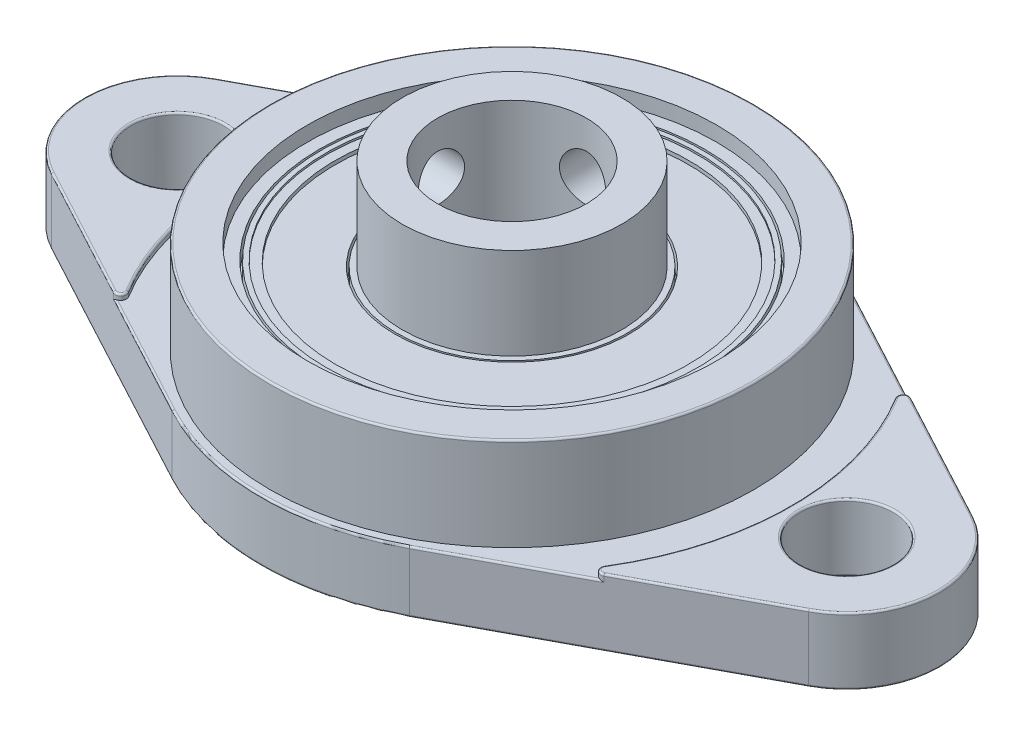
SolidWorks part; units mm, degrees
material "Q235"
ref_plane "前视" through (0, 0, 0) normal (0, 0, 1) x (1, 0, 0)
ref_plane "上视" through (0, 0, 0) normal (0, 1, 0) x (1, 0, 0)
ref_plane "右视" through (0, 0, 0) normal (1, 0, 0) x (0, 0, -1)
sketch "草图1" plane through (0, 0, 0) normal (0, 1, 0) x (1, 0, 0)
  line L0 (0, 0) -> (0, 23.9967) construction
  line L1 (-6.375, 11.9) -> (-20.3611, 4.4074)
  line L2 (0, 0) -> (-38.6632, 0) construction
  line L3 (-6.375, -11.9) -> (-20.3611, -4.4074)
  line L4 (6.375, -11.9) -> (20.3611, -4.4074)
  line L5 (6.375, 11.9) -> (20.3611, 4.4074)
  arc A0 (6.375, 11.9) -> (-6.375, 11.9) centre (0, 0) ccw
  arc A1 (20.3611, -4.4074) -> (20.3611, 4.4074) centre (18, 0) ccw
  circle A2 centre (18, 0) radius 2.5
  circle A3 centre (-18, 0) radius 2.5
  arc A4 (-20.3611, -4.4074) -> (-20.3611, 4.4074) centre (-18, 0) cw
  arc A5 (-6.375, -11.9) -> (6.375, -11.9) centre (0, 0) ccw
  circle A6 centre (0, 0) radius 4
  circle A7 centre (0, 0) radius 13.5 construction
  dimension "D1" = 27
  dimension "D2" = 10
  dimension "D4" = 5
  dimension "D5" = 8
  dimension "D6" = 27
  dimension "D3" = 36
extrude "凸台-拉伸1" add sketch "草图1" along normal blind 3.3
sketch "草图2" plane through (0, 3.3, 0) normal (0, 1, 0) x (1, 0, 0)
  line L0 (-6.375, 11.9) -> (-20.3611, 4.4074) construction
  line L1 (-13.1944, 8.2467) -> (-20.3611, 4.4074)
  line L2 (-20.3611, -4.4074) -> (-6.375, -11.9) construction
  line L3 (-20.3611, -4.4074) -> (-13.1944, -8.2467)
  line L4 (6.375, -11.9) -> (20.3611, -4.4074) construction
  line L5 (13.1944, -8.2467) -> (20.3611, -4.4074)
  line L6 (20.3611, 4.4074) -> (6.375, 11.9) construction
  line L7 (20.3611, 4.4074) -> (13.1944, 8.2467)
  circle A0 centre (0, 0) radius 13.5 construction
  arc A1 (-12.7968, 7.8258) -> (-12.7968, -7.8258) centre (0, 0) ccw
  arc A2 (-20.3611, 4.4074) -> (-20.3611, -4.4074) centre (-18, 0) ccw construction
  arc A3 (-20.3611, 4.4074) -> (-20.3611, -4.4074) centre (-18, 0) ccw
  arc A4 (20.3611, -4.4074) -> (20.3611, 4.4074) centre (18, 0) ccw construction
  arc A5 (20.3611, -4.4074) -> (20.3611, 4.4074) centre (18, 0) ccw
  circle A6 centre (0, 0) radius 15 construction
  arc A7 (12.7968, -7.8258) -> (12.7968, 7.8258) centre (0, 0) ccw
  arc A8 (12.7968, 7.8258) -> (13.1944, 8.2467) centre (13.0527, 7.9823) cw
  arc A9 (12.7968, -7.8258) -> (13.1944, -8.2467) centre (13.0527, -7.9823) ccw
  arc A10 (-12.7968, -7.8258) -> (-13.1944, -8.2467) centre (-13.0527, -7.9823) cw
  arc A11 (-12.7968, 7.8258) -> (-13.1944, 8.2467) centre (-13.0527, 7.9823) ccw
  circle A12 centre (-18, 0) radius 2.5 construction
  circle A13 centre (-18, 0) radius 2.5
  circle A14 centre (18, 0) radius 2.5 construction
  circle A15 centre (18, 0) radius 2.5
  dimension "D1" = 27
  dimension "D3" = 0.3
  dimension "D2" = 1.5
extrude "凸台-拉伸2" add sketch "草图2" along normal blind 0.3
sketch "草图3" plane through (0, 3.3, 0) normal (0, 1, 0) x (1, 0, 0)
  circle A0 centre (0, 0) radius 13
  circle A1 centre (0, 0) radius 4 construction
  circle A2 centre (0, 0) radius 4
  dimension "D1" = 26
extrude "凸台-拉伸3" add sketch "草图3" along normal blind 5
sketch "草图4" plane through (0, 8.3, 0) normal (0, 1, 0) x (1, 0, 0)
  circle A0 centre (0, 0) radius 11
  dimension "D1" = 22
extrude "切除-拉伸1" cut sketch "草图4" against normal blind 0.8
sketch "草图5" plane through (0, 7.5, 0) normal (0, 1, 0) x (1, 0, 0)
  circle A0 centre (0, 0) radius 10.35
  circle A1 centre (0, 0) radius 10.25
  dimension "D1" = 20.7
  dimension "D2" = 0.1
extrude "切除-拉伸2" cut sketch "草图5" against normal blind 0.8
sketch "草图6" plane through (0, 7.5, 0) normal (0, 1, 0) x (1, 0, 0)
  circle A0 centre (0, 0) radius 10
  dimension "D1" = 20
extrude "切除-拉伸3" cut sketch "草图6" against normal blind 0.1
sketch "草图7" plane through (0, 7.4, 0) normal (0, 1, 0) x (1, 0, 0)
  circle A0 centre (0, 0) radius 9.5
  dimension "D1" = 19
extrude "切除-拉伸4" cut sketch "草图7" against normal blind 0.2
sketch "草图8" plane through (0, 7.2, 0) normal (0, 1, 0) x (1, 0, 0)
  circle A0 centre (0, 0) radius 5.9
  circle A1 centre (0, 0) radius 4 construction
  circle A2 centre (0, 0) radius 4
  dimension "D1" = 11.8
extrude "凸台-拉伸4" add sketch "草图8" along normal blind 4.92
sketch "草图9" plane through (0, 7.2, 0) normal (0, 1, 0) x (1, 0, 0)
  circle A0 centre (0, 0) radius 5.9 construction
  circle A1 centre (0, 0) radius 5.9 construction
  circle A2 centre (0, 0) radius 6.2
  circle A3 centre (0, 0) radius 6.3
  dimension "D1" = 0.3
  dimension "D2" = 0.1
extrude "切除-拉伸5" cut sketch "草图9" against normal blind 1
fillet "圆角1" radius 0.1 30 edges at (-9.7847, 3.3, -10.0734) (0, 3.3, -13.5) (-9.7847, 3.3, 10.0734) (0, 3.3, 13.5) (-23, 0, 0) (-13.3681, 0, -8.1537) (0, 0, -13.5) (13.3681, 0, -8.1537) (23, 0, 0) (13.3681, 0, 8.1537) (0, 0, 13.5) (12.8346, 3.6, -8.1883) (16.7777, 3.6, -6.3271) (23, 3.6, 0) (16.7777, 3.6, 6.3271) (12.8346, 3.6, 8.1883) (-12.8346, 3.6, 8.1883) (-16.7777, 3.6, 6.3271) (-23, 3.6, 0) (-16.7777, 3.6, -6.3271) (-12.8346, 3.6, -8.1883) (-18, 3.6, 2.5) (18, 3.6, 2.5) (18, 0, 2.5) (9.7847, 3.3, -10.0734) (9.7847, 3.3, 10.0734) (-13.3681, 0, 8.1537) (0, 8.3, 13) (15, 3.6, 0) (-15, 3.6, 0)
sketch "草图10" plane through (0, 0, 0) normal (1, 0, 0) x (0, 0, -1)
  line L0 (4, 12.12) -> (-4, 12.12) construction
  circle A0 centre (0, 9.32) radius 1.25
  dimension "D1" = 2.5
  dimension "D2" = 2.8
extrude "切除-拉伸6" cut sketch "草图10" against normal blind 9
sketch "草图11" plane through (0, 0, 0) normal (0, 0, 1) x (1, 0, 0)
  line L0 (5.9, 12.12) -> (-5.9, 12.12) construction
  circle A0 centre (0, 9.32) radius 1.25
  dimension "D1" = 2.5
  dimension "D2" = 2.8
extrude "切除-拉伸7" cut sketch "草图11" against normal blind 9
sketch "草图12" plane through (0, 0, 0) normal (0, -1, 0) x (1, 0, 0)
  line L2 (-19.7, 3.1733) -> (-5.7139, 10.6659)
  line L3 (-16.2724, 5.0095) -> (-5.7139, 10.6659)
  line L5 (5.7139, 10.6659) -> (19.7, 3.1733)
  line L6 (5.7139, 10.6659) -> (16.2724, 5.0095)
  line L8 (-5.7139, -10.6659) -> (-19.7, -3.1733)
  line L9 (-5.7139, -10.6659) -> (-16.2724, -5.0095)
  line L11 (19.7, -3.1733) -> (5.7139, -10.6659)
  line L12 (16.2724, -5.0095) -> (5.7139, -10.6659)
  arc A3 (5.7139, 10.6659) -> (-5.7139, 10.6659) centre (0, 0) ccw
  arc A4 (5.7139, 10.6659) -> (-5.7139, 10.6659) centre (0, 0) ccw
  arc A6 (-5.7139, -10.6659) -> (5.7139, -10.6659) centre (0, 0) ccw
  arc A7 (-5.7139, -10.6659) -> (5.7139, -10.6659) centre (0, 0) ccw
  circle A9 centre (-18, 0) radius 4.8
  arc A10 (-16.2407, -4.466) -> (-16.2407, 4.466) centre (-18, 0) ccw
  arc A11 (16.2407, 4.466) -> (16.2724, 5.0095) centre (16.1307, 4.7451) ccw
  circle A12 centre (18, 0) radius 4.8
  arc A13 (16.2407, 4.466) -> (16.2407, -4.466) centre (18, 0) ccw
  arc A14 (16.2407, -4.466) -> (16.2724, -5.0095) centre (16.1307, -4.7451) cw
  arc A15 (-16.2407, -4.466) -> (-16.2724, -5.0095) centre (-16.1307, -4.7451) ccw
  arc A16 (-16.2407, 4.466) -> (-16.2724, 5.0095) centre (-16.1307, 4.7451) cw
  circle A17 centre (0, 0) radius 10.375
  dimension "D1" = 1.4
  dimension "D9" = 0.3
  dimension "D10" = 20.75
  dimension "D2" = 1.4
  dimension "D3" = 1.4
  dimension "D4" = 1.4
  dimension "D5" = 1.4
  dimension "D6" = 1.4
  dimension "D7" = 2.3
  dimension "D8" = 2.3
extrude "切除-拉伸8" cut sketch "草图12" against normal blind 0.6
sketch "草图13" plane through (0, 0, 0) normal (0, -1, 0) x (1, 0, 0)
  circle A1 centre (0, 0) radius 9.675
  circle A2 centre (0, 0) radius 9.575
  circle A3 centre (0, 0) radius 9.575
  dimension "D1" = 0.8
  dimension "D2" = 0.1
extrude "切除-拉伸9" cut sketch "草图13" against normal blind 1
sketch "草图14" plane through (0, 0, 0) normal (0, -1, 0) x (1, 0, 0)
  circle A1 centre (0, 0) radius 6.2
  circle A2 centre (0, 0) radius 6
  circle A3 centre (0, 0) radius 6
  dimension "D1" = 2
  dimension "D2" = 0.2
extrude "切除-拉伸10" cut sketch "草图14" against normal blind 1
sketch "草图15" plane through (0, 0.6, 0) normal (0, -1, 0) x (1, 0, 0)
  line L0 (0, 0) -> (-26.2728, 0) construction
  line L1 (-10.1634, 4.7) -> (-9.2494, 4.7)
  line L2 (-10.1634, -4.7) -> (-9.2494, -4.7)
  line L3 (9.2494, -4.7) -> (10.1634, -4.7)
  line L4 (9.2494, 4.7) -> (10.1634, 4.7)
  circle A1 centre (0, 0) radius 10.375 construction
  circle A2 centre (0, 0) radius 11.375
  arc A3 (10.4388, -4.5192) -> (10.4388, 4.5192) centre (0, 0) ccw
  arc A4 (9.2494, -4.7) -> (9.2494, 4.7) centre (0, 0) ccw
  arc A5 (-10.4388, 4.5192) -> (-10.4388, -4.5192) centre (0, 0) ccw
  arc A6 (-9.2494, 4.7) -> (-9.2494, -4.7) centre (0, 0) ccw
  arc A7 (10.1634, 4.7) -> (10.4388, 4.5192) centre (10.1634, 4.4) cw
  arc A8 (10.1634, -4.7) -> (10.4388, -4.5192) centre (10.1634, -4.4) ccw
  arc A9 (-10.1634, -4.7) -> (-10.4388, -4.5192) centre (-10.1634, -4.4) cw
  arc A10 (-10.4388, 4.5192) -> (-10.1634, 4.7) centre (-10.1634, 4.4) cw
  dimension "D3" = 0.3
  dimension "D1" = 9.4
  dimension "D2" = 1
extrude "切除-拉伸11" cut sketch "草图15" against normal blind 3
